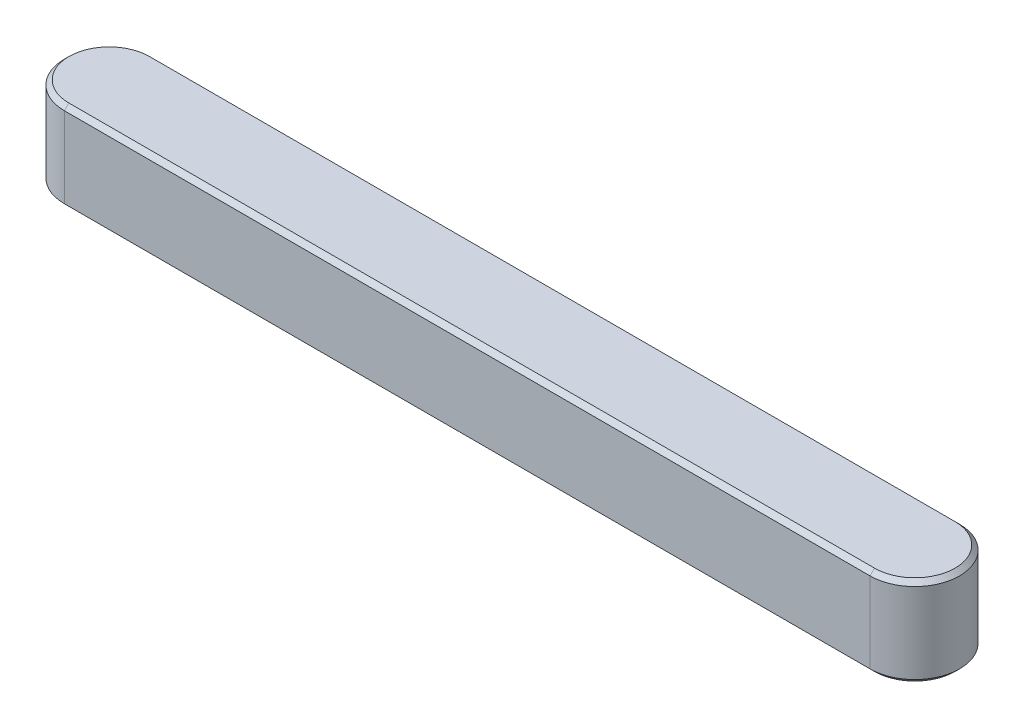
SolidWorks part; units mm, degrees
material "S45C"
ref_plane "Front Plane" through (0, 0, 0) normal (0, 0, 1) x (1, 0, 0)
ref_plane "Top Plane" through (0, 0, 0) normal (0, 1, 0) x (1, 0, 0)
ref_plane "Right Plane" through (0, 0, 0) normal (1, 0, 0) x (0, 0, -1)
sketch "Sketch1" plane through (0, 0, 0) normal (0, 1, 0) x (1, 0, 0)
  line L0 (-30, 0) -> (30, 0) construction
  line L1 (0, 3) -> (0, -3) construction
  line L3 (-30, 3) -> (30, 3)
  line L4 (-30, 3) -> (-30, -3)
  line L5 (-30, -3) -> (30, -3)
  line L6 (30, 3) -> (30, -3)
  dimension "L" = 60
  dimension "B" = 6
extrude "Boss-Extrude1" add sketch "Sketch1" along normal blind 6
chamfer "Chamfer1" [suppressed] distance 0.3 angle 45
fillet "Fillet1" 2 edges at (-30, 3, 3) (-30, 3, -3) type full round first side face at (0, 3, 3) second side face at (0, 3, -3) middle face at (-30, 3, 0)
fillet "Fillet2" 2 edges at (30, 3, 3) (30, 3, -3) type full round first side face at (1.5, 3, 3) second side face at (1.5, 3, -3) middle face at (30, 3, 0)
chamfer "Chamfer2" distance 0.3 angle 45 8 edges at (0, 0, -3) (-30, 0, 0) (30, 0, 0) (0, 0, 3) (0, 6, -3) (-30, 6, 0) (30, 6, 0) (0, 6, 3)
